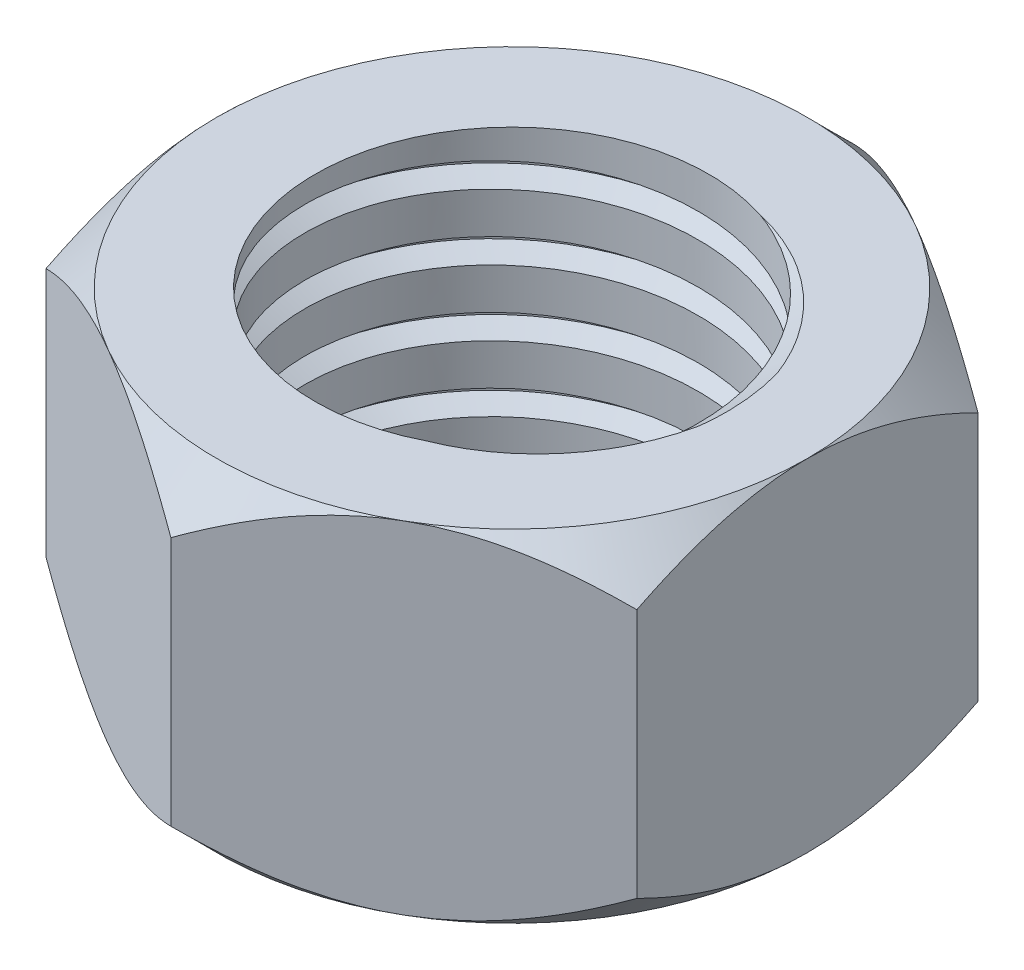
SolidWorks part; units mm, degrees
ref_plane "Front Plane" through (0, 0, 0) normal (0, 0, 1) x (1, 0, 0)
ref_plane "Top Plane" through (0, 0, 0) normal (0, 1, 0) x (1, 0, 0)
ref_plane "Right Plane" through (0, 0, 0) normal (1, 0, 0) x (0, 0, -1)
sketch "Sketch1" plane through (0, 0, 0) normal (0, 1, 0) x (1, 0, 0)
  line L1 (0, 10.3923) -> (-9, 5.1962)
  line L2 (-9, 5.1962) -> (-9, -5.1962)
  line L3 (-9, -5.1962) -> (0, -10.3923)
  line L4 (0, -10.3923) -> (9, -5.1962)
  line L5 (9, -5.1962) -> (9, 5.1962)
  line L6 (9, 5.1962) -> (0, 10.3923)
  circle A0 centre (0, 0) radius 9 construction
  dimension "D2" = 18
extrude "Boss-Extrude1" add sketch "Sketch1" along normal mid plane 10.4
sketch "Sketch9" plane through (0, 5.2, 0) normal (0, 1, 0) x (1, 0, 0)
  circle A0 centre (0, 0) radius 9
  dimension "D1" = 18
extrude "Cut-Extrude3" cut sketch "Sketch9" against normal through all draft 45 flip side to cut
mirror "Mirror1" about plane through (0, 0, 0) normal (0, 1, 0) of "Cut-Extrude3"
sketch "Sketch10" plane through (0, 5.2, 0) normal (0, 1, 0) x (1, 0, 0)
  circle A0 centre (0, 0) radius 6
  dimension "D1" = 12
extrude "Cut-Extrude4" cut sketch "Sketch10" against normal through all
thread "Thread1" pitch 1 start angle 0, offset 2, length 10.4, pitch 2, diameter 12
ref_plane "Plane2" through (6, -7.2, 0) normal (0, 0, 1) x (1, 0, 0)
sketch "Thread Profile2" plane through (6, -7.2, 0) normal (0, 0, 1) x (1, 0, 0)
  line L0 (0, 0) -> (0, 1) construction
  line L1 (0, 0) -> (0.5413, 0.3125)
  line L2 (0.5413, 0.3125) -> (0.5413, 0.4375)
  line L3 (0.5413, 0.4375) -> (0, 0.75)
  line L4 (0.5413, 0.375) -> (0, 0.375) construction
  line L11 (0, 0) -> (0, 0.75)
  point P2 (0, 0)
  dimension "Pitch" = 1
  dimension "Profile_Angle" = 60
  dimension "Profile_Land" = 0.125
  dimension "Profile_Height" = 0.5413
